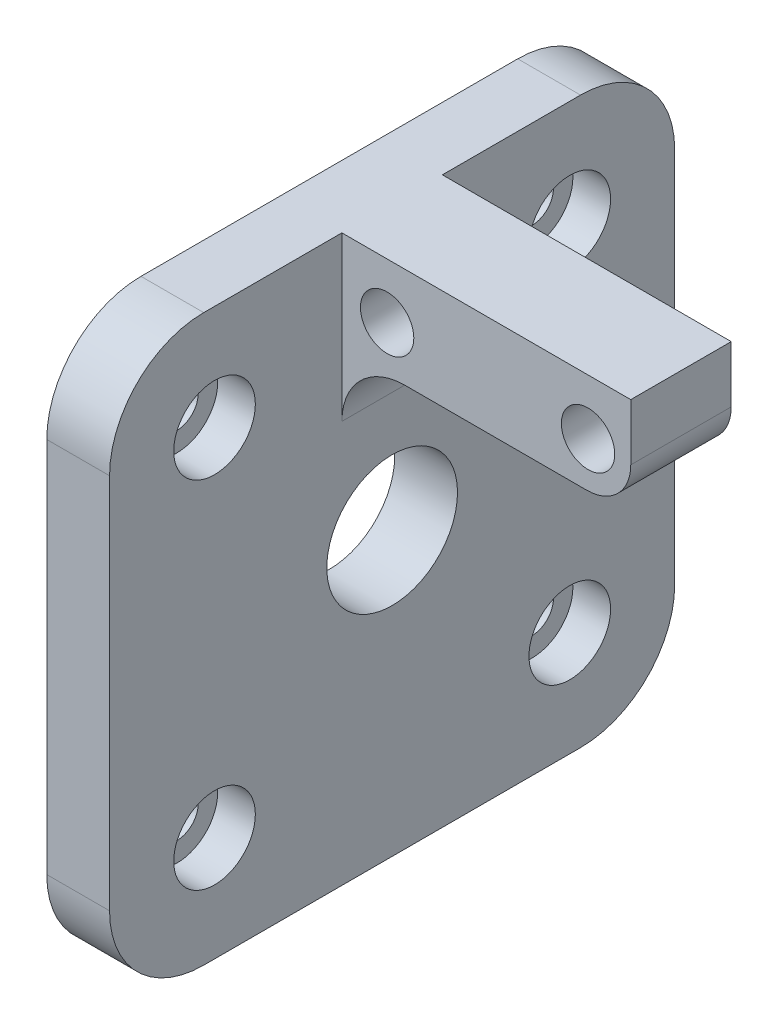
SolidWorks part; units mm, degrees
ref_plane "Front Plane" through (0, 0, 0) normal (0, 0, 1) x (1, 0, 0)
ref_plane "Top Plane" through (0, 0, 0) normal (0, 1, 0) x (1, 0, 0)
ref_plane "Right Plane" through (0, 0, 0) normal (1, 0, 0) x (0, 0, -1)
sketch "Sketch1" plane through (0, 0, 0) normal (1, 0, 0) x (0, 0, -1)
  line L1 (-22.5, -22.5) -> (22.5, -22.5)
  line L2 (-22.5, -22.5) -> (-22.5, 22.5)
  line L3 (-22.5, 22.5) -> (22.5, 22.5)
  line L4 (22.5, -22.5) -> (22.5, 22.5)
  line L5 (-22.5, -22.5) -> (22.5, 22.5) construction
  line L6 (-22.5, 22.5) -> (22.5, -22.5) construction
  line L7 (-4, 22.5) -> (4, 22.5)
  line L8 (-4, 22.5) -> (-4, 14.5)
  line L9 (-4, 14.5) -> (4, 14.5)
  line L10 (4, 22.5) -> (4, 14.5)
  circle A0 centre (0, 0) radius 5.205
  circle A1 centre (0, 0) radius 20 construction
  point P12 (0, 22.5)
  point P13 (0, 0)
  point P14 (2.0207, 4.7275)
  point P15 (0, 14.5)
  point P16 (0, 0)
  point P17 (4, 6.705)
  point P18 (4, 14.0777)
  dimension "D1" = 10.41
  dimension "D4" = 40
  dimension "D2" = 8
  dimension "D3" = 45
  dimension "D5" = 8
extrude "Boss-Extrude1" add sketch "Sketch1" along normal blind 5 contours L3 L10 L9 L8 L2 L1 L4 A0 | L10 L3 L8 L9 region at (0, 0, 21.8636) region at (0, 18.5, 0)
extrude "Boss-Extrude2" add sketch "Sketch1<3>" along normal blind 28 contours L10 L3 L8 L9 region at (0, 18.5, 0)
sketch "Sketch1<3>" plane through (0, 0, 0) normal (1, 0, 0) x (0, 0, -1) same geometry as "Sketch1"
fillet "Fillet1" radius 7.5 4 edges at (2.5, -22.5, 22.5) (2.5, -22.5, -22.5) (2.5, 22.5, -22.5) (2.5, 22.5, 22.5)
fillet "Fillet2" radius 5 1 edges at (5, 14.5, 0)
fillet "Fillet3" radius 3.5 1 edges at (28, 14.5, 0)
sketch "Sketch2" plane through (0, 0, 0) normal (0, 0, 1) x (1, 0, 0)
  circle A0 centre (24.6, 18.1) radius 3.1 construction
  circle A1 centre (8.6, 18.1) radius 3.1
  circle A2 centre (8.6, 18.1) radius 3.1 construction
  circle A3 centre (24.6, 18.1) radius 3.1 construction
  circle A4 centre (8.6, 18.1) radius 2.125
  circle A5 centre (24.6, 18.1) radius 2.125
  dimension "D2" = 4.25
  dimension "D3" = 4.25
  dimension "D1" = 0
extrude "Cut-Extrude1" cut sketch "Sketch2" against normal through all both and the other way through all
hole_wizard "CBORE for M3 SHCS1" positions "Sketch5" profile "Sketch7" counterbore size "M3" standard "ANSI Metric" end condition through all
sketch "Sketch5" plane through (5, 0, 0) normal (1, 0, 0) x (0, 0, -1)
  line L0 (-22.5, 22.5) -> (22.5, -22.5) construction
  line L1 (-22.5, -22.5) -> (22.5, 22.5) construction
  circle A0 centre (0, 0) radius 20 construction
  point P0 (-14.1421, 14.1421)
  point P6 (14.1421, 14.1421)
  point P10 (-14.1421, -14.1421)
  point P12 (14.1421, -14.1421)
sketch "Sketch7" plane through (5, 14.1421, 14.1421) normal (0, 1, 0) x (0, 0, -1)
  line L0 (0, 0) -> (0, 5)
  line L1 (0, 5) -> (1.7, 5)
  line L3 (1.7, 5) -> (1.7, 3)
  line L4 (1.7, 3) -> (3.25, 3)
  line L5 (3.25, 3) -> (3.25, 0)
  line L7 (3.25, 0) -> (0, 0)
  line L11 (0, -6.35) -> (0, 107.95) construction
  dimension "Thru Hole Dia." = 3.4
  dimension "Thru Hole Depth" = 5
  dimension "C'Bore Dia." = 6.5
  dimension "C'Bore Depth" = 3
